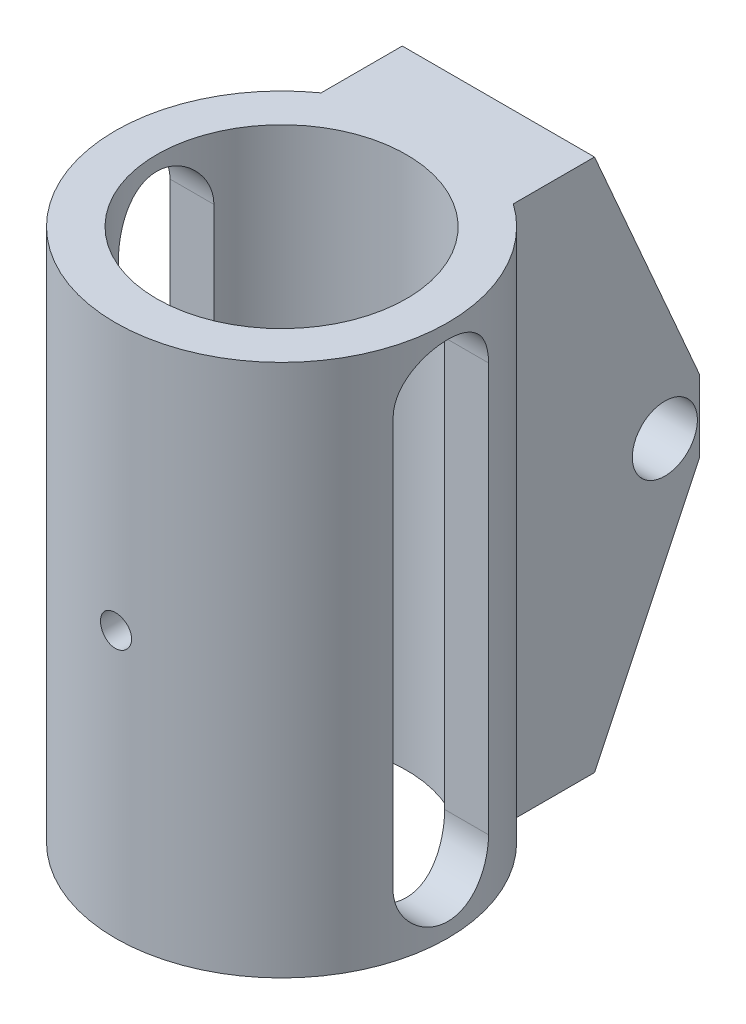
SolidWorks part; units mm, degrees
ref_plane "Front Plane" through (0, 0, 0) normal (0, 0, 1) x (1, 0, 0)
ref_plane "Top Plane" through (0, 0, 0) normal (0, 1, 0) x (1, 0, 0)
ref_plane "Right Plane" through (0, 0, 0) normal (1, 0, 0) x (0, 0, -1)
sketch "Sketch1" plane through (0, 0, 0) normal (0, 1, 0) x (1, 0, 0)
  circle A0 centre (0, 0) radius 8.6383
  circle A1 centre (0, 0) radius 11.5
  dimension "D1" = 17.2766
  dimension "D2" = 23
extrude "Boss-Extrude1" add sketch "Sketch1" along normal blind 36.88
ref_plane "Plane1" through (-11.5, 0, 0) normal (-1, 0, 0) x (0, 0, 1)
sketch "Sketch2" plane through (-11.5, 0, 0) normal (-1, 0, 0) x (0, 0, 1)
  line L0 (0, 32.5733) -> (0, 4.3067) construction
  line L1 (3.302, 32.5733) -> (3.302, 4.3067)
  line L2 (-3.302, 32.5733) -> (-3.302, 4.3067)
  line L3 (0, 32.5733) -> (0, 36.88) construction
  line L4 (8.6383, 36.88) -> (-8.6383, 36.88) construction
  line L5 (0, 4.3067) -> (0, 0) construction
  arc A0 (3.302, 32.5733) -> (-3.302, 32.5733) centre (0, 32.5733) ccw
  arc A1 (-3.302, 4.3067) -> (3.302, 4.3067) centre (0, 4.3067) ccw
  point P3 (0, 18.44)
  dimension "D1" = 3.302
extrude "Cut-Extrude1" cut sketch "Sketch2" against normal blind 55.88
sketch "Sketch3" plane through (0, 0, 0) normal (0, 0, 1) x (1, 0, 0)
  line L0 (0, 36.88) -> (0, 18.44) construction
  line L1 (11.5, 36.88) -> (-11.5, 36.88) construction
  circle A0 centre (0, 18.44) radius 1.0754
extrude "Cut-Extrude2" cut sketch "Sketch3" along normal through all
sketch "Sketch4" plane through (0, 0, 0) normal (0, 0, 1) x (1, 0, 0)
  line L0 (-8.6383, 0) -> (-6.6495, 0) construction
  line L5 (8.6383, 0) -> (6.6495, 0) construction
  line L6 (8.6383, 36.88) -> (6.6495, 36.88) construction
  line L7 (-8.6383, 36.88) -> (-6.6495, 36.88) construction
  line L9 (6.6495, 0) -> (-6.6495, 0)
  line L10 (6.6495, 0) -> (6.6495, 36.88)
  line L11 (6.6495, 36.88) -> (-6.6495, 36.88)
  line L12 (-6.6495, 0) -> (-6.6495, 36.88)
extrude "Boss-Extrude2" add sketch "Sketch4" along normal up to surface (5.6174 mm away) from offset 15 up to face at (11.2557, 18.44, 0) offset against normal yes
sketch "Sketch5" plane through (-6.6495, 0, 0) normal (-1, 0, 0) x (0, 0, 1)
  line L0 (-22.264, 15.2344) -> (-22.264, 20.2202)
  line L1 (-15, 36.88) -> (-22.264, 20.2202)
  line L2 (-22.264, 15.2344) -> (-15, 0)
  line L3 (-15, 17.577) -> (-19.8654, 17.577) construction
  line L4 (-15, 36.88) -> (-15, 0) construction
  circle A0 centre (-19.8654, 17.577) radius 2.25
  point P0 (-19.8654, 17.577)
  point P4 (-23.1961, 17.9759)
  point P6 (-22.2657, 17.577)
  point P11 (-23.286, 17.6423)
  point P12 (0, 0)
  point P17 (-23.381, 17.6177)
  point P18 (-23.2009, 17.577)
  line M4 (-15, 36.88) -> (-15, 0)
  dimension "D1" = 4.5
extrude "Boss-Extrude3" add sketch "Sketch5" along direction (-1, 0, 0) on the side against the normal up to surface (13.299 mm away) contours L0 L2 L1 A0 M4 region at (-6.6495, 18.2439, -17.4579) up to face at (6.6495, 18.44, -12.1913)
